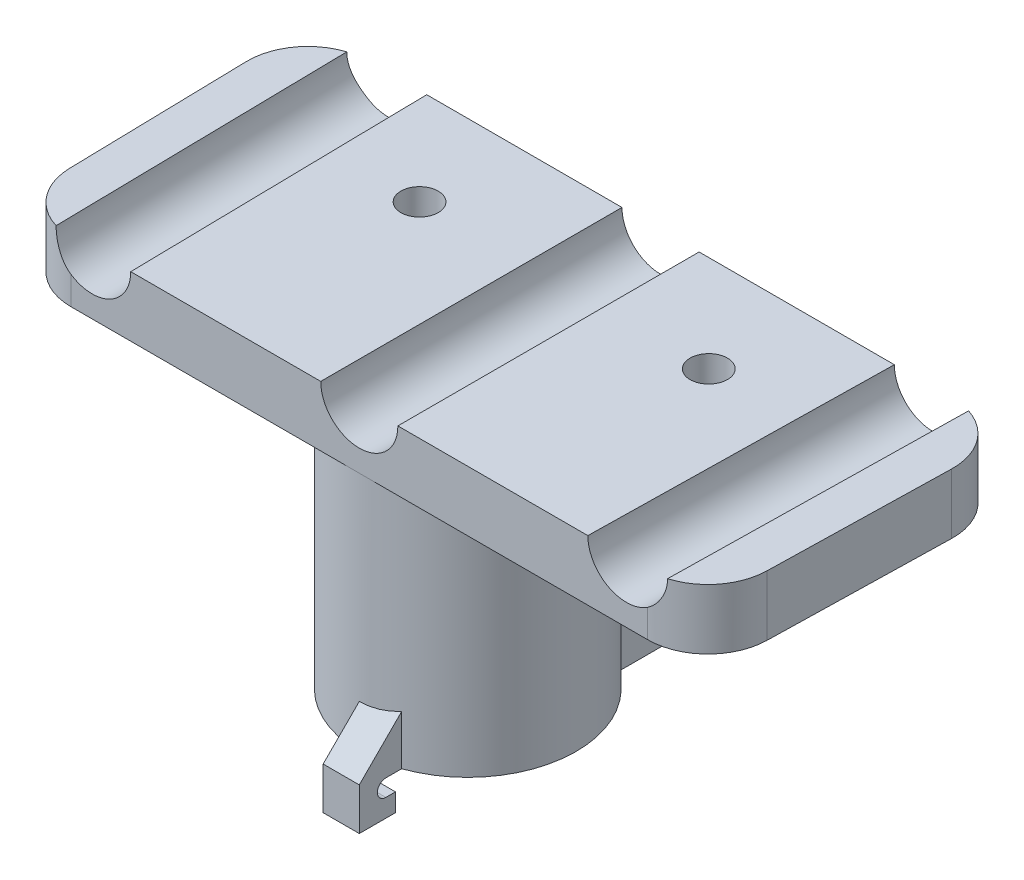
SolidWorks part; units mm, degrees
ref_plane "Front Plane" through (0, 0, 0) normal (0, 0, 1) x (1, 0, 0)
ref_plane "Top Plane" through (0, 0, 0) normal (0, 1, 0) x (1, 0, 0)
ref_plane "Right Plane" through (0, 0, 0) normal (1, 0, 0) x (0, 0, -1)
sketch "Sketch1" plane through (0, 0, 0) normal (0, 1, 0) x (1, 0, 0)
  line L0 (-28.8203, 0) -> (-29.3877, 25)
  line L1 (-29.3877, 25) -> (29.3877, 25)
  line L2 (29.3877, 25) -> (28.8203, 0)
  line L3 (28.8203, 0) -> (-28.8203, 0)
  line L4 (0, 0) -> (0, 43.9643) construction
  point P4 (0, -1270)
  point P8 (0, 0)
  dimension "D1" = 1270
  dimension "D2" = 1.3
  dimension "D3" = 25
extrude "Boss-Extrude1" add sketch "Sketch1" along normal blind 5
sketch "Sketch2" plane through (0, 0, 0) normal (0, -1, 0) x (1, 0, 0)
  circle A0 centre (0, -9) radius 9
  circle A1 centre (0, -9) radius 6
  dimension "D1" = 18
  dimension "D2" = 12
extrude "Boss-Extrude2" add sketch "Sketch2" along normal blind 20
sketch "Sketch3" plane through (0, 0, 0) normal (0, -1, 0) x (1, 0, 0)
  line L0 (29.3877, -25) -> (-29.3877, -25) construction
  line L1 (5, -16.4833) -> (-5, -16.4833)
  line L2 (5, -16.4833) -> (5, -25)
  line L3 (5, -25) -> (-5, -25)
  line L4 (-5, -16.4833) -> (-5, -25)
  circle A0 centre (0, -9) radius 9 construction
  circle A1 centre (0, -9) radius 9 construction
  dimension "D1" = 10
extrude "Boss-Extrude3" add sketch "Sketch3" along normal blind 20
sketch "Sketch5" plane through (0, 0, 0) normal (0, 0, 1) x (1, 0, 0)
  line L0 (-28.8203, 5) -> (28.8203, 5) construction
  circle A0 centre (0, 5) radius 3.2
  dimension "D1" = 6.4
extrude "Cut-Extrude1" cut sketch "Sketch5" against normal through all both and the other way through all
ref_axis "Axis1" through (0, 0, 1270) along (0, 1, 0)
pattern_circular "CirPattern1" count 2 every 1 about axis through (0, 0, 1270) along (0, 1, 0) of "Cut-Extrude1" other way count 2
sketch "Sketch6" plane through (0, 0, -25) normal (0, 0, -1) x (-1, 0, 0)
  line L0 (5, 0) -> (29.3877, 0) construction
  circle A0 centre (0, -13) radius 2
  point P6 (0, 0)
  dimension "D1" = 4
  dimension "D2" = 13
extrude "Cut-Extrude2" cut sketch "Sketch6" against normal up to next and the other way through all
sketch "Sketch7" plane through (0, 0, -25) normal (0, 0, -1) x (-1, 0, 0)
  line L0 (-3.55, -15.0496) -> (-3.55, -20)
  line L1 (0, -17.0992) -> (3.55, -15.0496) construction
  line L2 (3.55, -15.0496) -> (3.55, -10.9504)
  line L3 (3.55, -10.9504) -> (0, -8.9008)
  line L4 (0, -8.9008) -> (-3.55, -10.9504)
  line L5 (-3.55, -10.9504) -> (-3.55, -15.0496)
  line L6 (-3.55, -15.0496) -> (0, -17.0992) construction
  line L7 (5, -20) -> (-5, -20) construction
  line L8 (-3.55, -20) -> (3.55, -20)
  line L9 (3.55, -20) -> (3.55, -15.0496)
  circle A0 centre (0, -13) radius 3.55 construction
  dimension "D1" = 7.1
extrude "Cut-Extrude3" cut sketch "Sketch7" against normal blind 3 from offset 3.3 offset against normal yes
sketch "Sketch8" plane through (0, 0, 0) normal (1, 0, 0) x (0, 0, -1)
  line L0 (1, -15.4) -> (-3, -19.4)
  line L1 (-3, -19.4) -> (-3, -22.9)
  line L3 (1, -20) -> (1, -15.4)
  line L4 (0, 0) -> (0, -20) construction
  line L5 (1, -20) -> (-0.8, -20)
  line L10 (0, -20) -> (16.4833, -20) construction
  line L11 (-0.8, -21.4) -> (0, -21.4)
  line L12 (0, -21.4) -> (0, -22.9)
  line L13 (0, -22.9) -> (-3, -22.9)
  arc A2 (-0.8, -20) -> (-0.8, -21.4) centre (-0.8, -20.7) ccw
  dimension "D6" = 1.5
  dimension "D5" = 0.7
  dimension "D1" = 1
  dimension "D2" = 3
  dimension "D3" = 45
  dimension "D4" = 3.5
  dimension "D7" = 0.8
extrude "Boss-Extrude4" add sketch "Sketch8" along normal blind 3
fillet "Fillet1" radius 5 4 edges at (28.8203, 2.5, 0) (29.3877, 2.5, -25) (-28.8203, 2.5, 0) (-29.3877, 2.5, -25)
sketch "Sketch9" plane through (0, 0, 0) normal (0, -1, 0) x (1, 0, 0)
  line L0 (24.2729, -25) -> (5, -25) construction
  line L1 (12, -20.2332) -> (14.8, -18.6166)
  line L2 (14.8, -18.6166) -> (14.8, -15.3834)
  line L3 (14.8, -15.3834) -> (12, -13.7668)
  line L4 (12, -13.7668) -> (9.2, -15.3834)
  line L5 (9.2, -15.3834) -> (9.2, -18.6166)
  line L6 (9.2, -18.6166) -> (12, -20.2332)
  circle A0 centre (12, -17) radius 2.8 construction
  dimension "D1" = 12
  dimension "D2" = 5.6
  dimension "D3" = 8
extrude "Cut-Extrude4" cut sketch "Sketch9" against normal blind 1
sketch "Sketch10" plane through (0, 1, 0) normal (0, -1, 0) x (1, 0, 0)
  circle A0 centre (12, -17) radius 1.55
  dimension "D1" = 3.1
extrude "Cut-Extrude5" cut sketch "Sketch10" against normal through all
mirror "Mirror1" about plane through (0, 0, 0) normal (1, 0, 0) of "Cut-Extrude5", "Cut-Extrude4"
sketch "Sketch11" [suppressed] plane through (0, 0, 0) normal (0, -1, 0) x (1, 0, 0)
  line L1 (24.2729, -25) -> (-24.2729, -25) construction
  line L2 (0, 0) -> (0, -25) construction
  line L3 (-23.9325, 0) -> (23.9325, 0) construction
  circle A0 centre (12, -17) radius 1.6
  circle A2 centre (-12, -17) radius 1.6
  dimension "D3" = 3.2
  dimension "D1" = 12
  dimension "D2" = 8
extrude "Cut-Extrude6" [suppressed] cut sketch "Sketch11" against normal through all
equation "\"dtheta\"=1"
equation "\"D2@Sketch1\"=\"dtheta\"+0.3"
